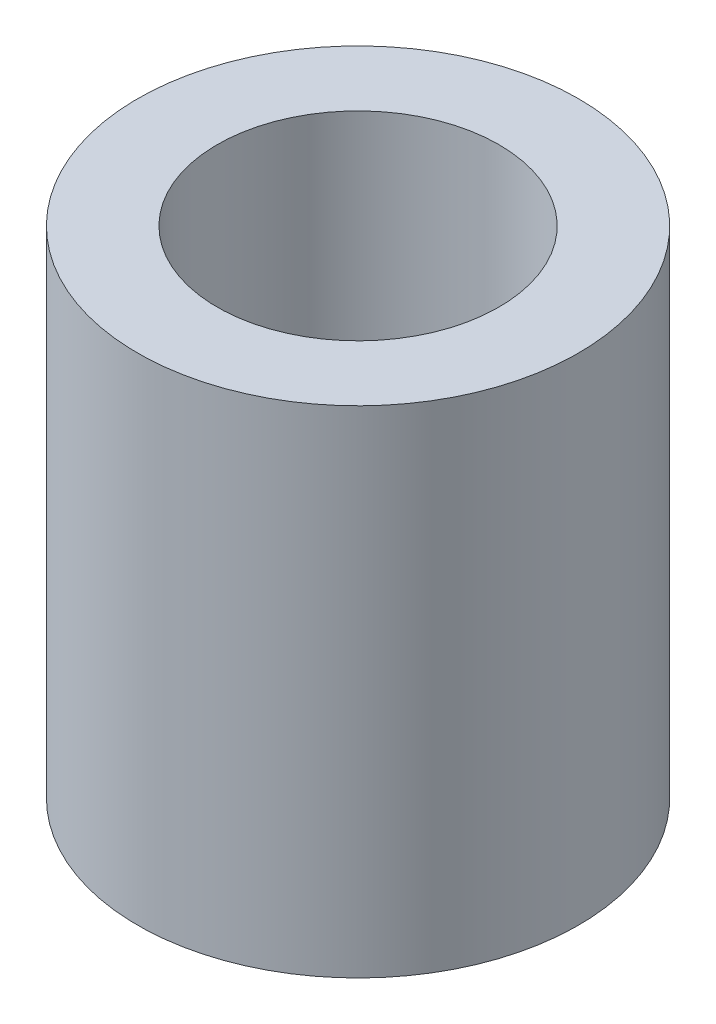
SolidWorks part; units mm, degrees
ref_plane "Front Plane" through (0, 0, 0) normal (0, 0, 1) x (1, 0, 0)
ref_plane "Top Plane" through (0, 0, 0) normal (0, 1, 0) x (1, 0, 0)
ref_plane "Right Plane" through (0, 0, 0) normal (1, 0, 0) x (0, 0, -1)
sketch "Sketch1" plane through (0, 0, 0) normal (0, 1, 0) x (1, 0, 0)
  circle A0 centre (0, 0) radius 17.5
  dimension "SLEEVE_OD" = 35
extrude "Boss-Extrude1" add sketch "Sketch1" along normal blind 39.3484
sketch "Sketch2" plane through (0, 0, 0) normal (0, 1, 0) x (1, 0, 0)
  circle A0 centre (0, 0) radius 11.1825
  dimension "BORE_D" = 22.365
extrude "Cut-Extrude1" cut sketch "Sketch2" along normal through all
chamfer "Chamfer1" distance 2.4482 angle 60 rebuild error yes
